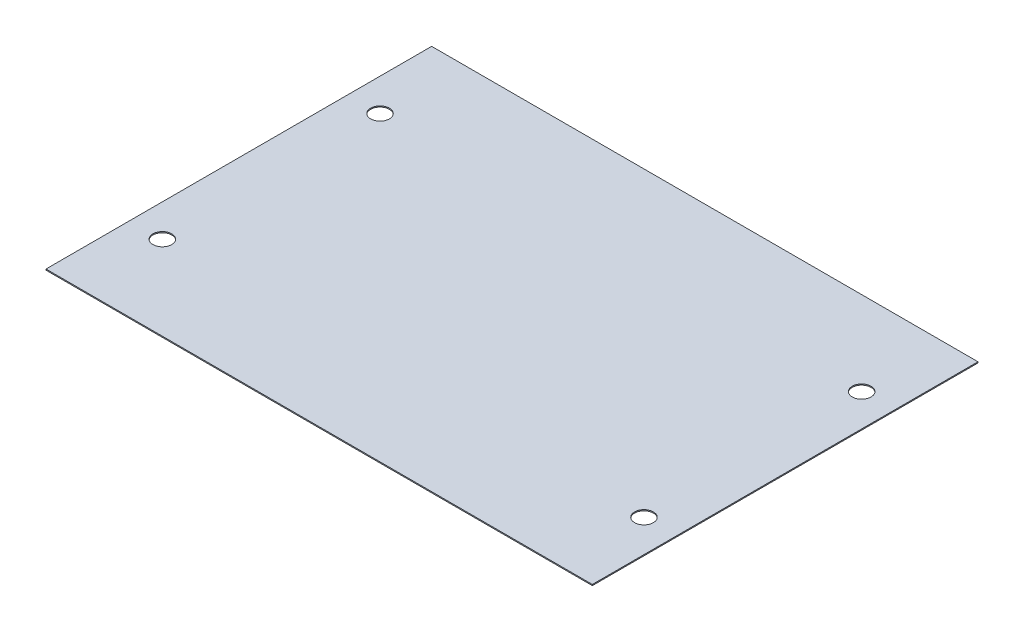
SolidWorks part; units mm, degrees
ref_plane "Front Plane" through (0, 0, 0) normal (0, 0, 1) x (1, 0, 0)
ref_plane "Top Plane" through (0, 0, 0) normal (0, 1, 0) x (1, 0, 0)
ref_plane "Right Plane" through (0, 0, 0) normal (1, 0, 0) x (0, 0, -1)
sketch "Sketch2" plane through (0, 0, 0) normal (0, 1, 0) x (1, 0, 0)
  line L4 (-49.9289, 21.4313) -> (-49.9289, -14.5687)
  line L5 (-49.9289, -14.5687) -> (1.0711, -14.5687)
  line L6 (-49.9289, 21.4313) -> (-49.9289, -14.5687)
  line L7 (1.0711, 21.4313) -> (-49.9289, 21.4313)
  line L9 (-49.9289, -14.5687) -> (1.0711, -14.5687)
  line L11 (1.0711, 21.4313) -> (-49.9289, 21.4313)
  line L20 (1.0711, -14.5687) -> (1.0711, 21.4313)
  line L21 (1.0711, -14.5687) -> (1.0711, 21.4313)
  circle A20 centre (-1.9489, 13.5913) radius 0.875 construction
  circle A21 centre (-46.9089, 13.5913) radius 0.875 construction
  circle A22 centre (-46.9089, -6.7287) radius 0.875 construction
  circle A23 centre (-1.9489, -6.7287) radius 0.875 construction
  circle A24 centre (-1.9489, 13.5913) radius 0.875
  circle A25 centre (-46.9089, 13.5913) radius 0.875
  circle A26 centre (-46.9089, -6.7287) radius 0.875
  circle A27 centre (-1.9489, -6.7287) radius 0.875
  dimension "D1" = 0
extrude "Boss-Extrude2" add sketch "Sketch2" along normal blind 0.1
